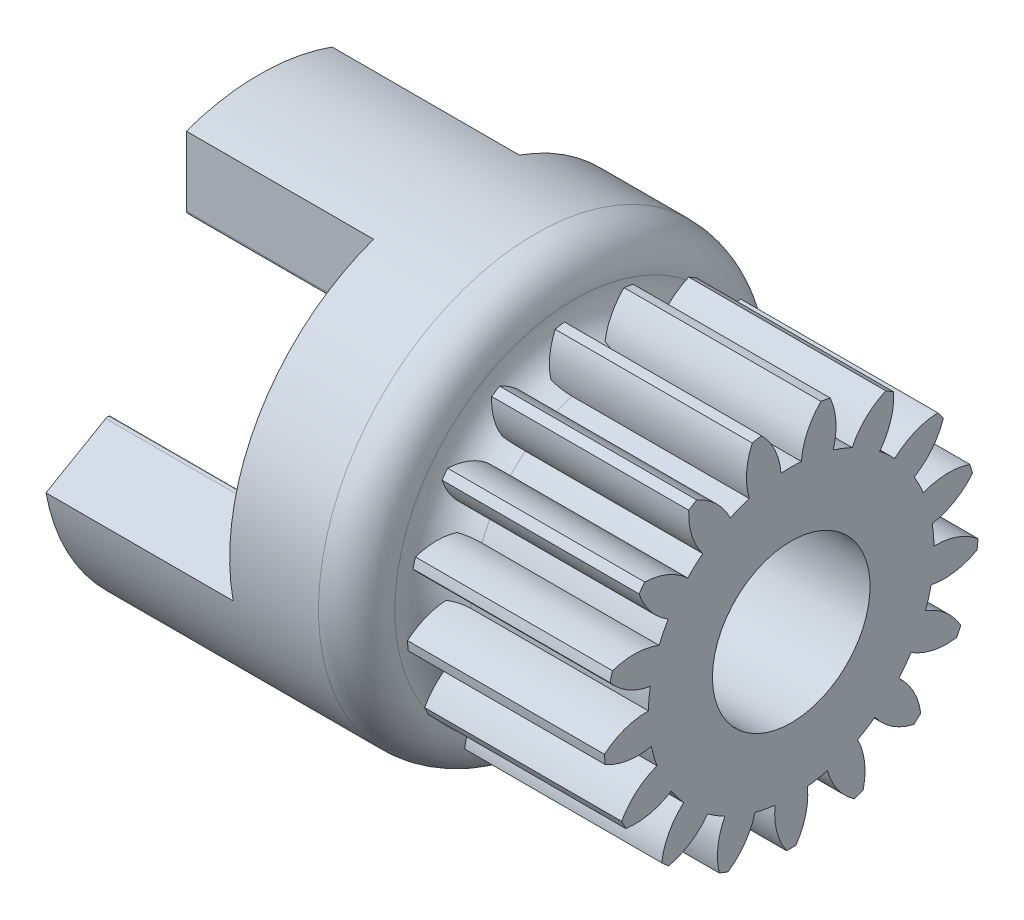
SolidWorks part; units mm, degrees
ref_plane "Plane1" through (0, 0, 0) normal (0, 0, 1) x (1, 0, 0)
ref_plane "Plane2" through (0, 0, 0) normal (0, 1, 0) x (1, 0, 0)
ref_plane "Plane3" through (0, 0, 0) normal (1, 0, 0) x (0, 0, -1)
sketch "HoldingSke" plane through (0, 0, 0) normal (0, 1, 0) x (1, 0, 0)
  line L0 (0, 0) -> (0.9563, -0.2924)
  line L1 (-15, 0) -> (100, 0) construction
  line L2 (0, 0) -> (-2.1039, 2.3779)
  line L3 (0, 0) -> (-11.863, 4.5341)
  line L4 (0, 0) -> (8.2586, 2.5249)
  line L5 (0, 0) -> (-46.8476, -17.4728)
  line L6 (0, 0) -> (-8.2896, -5.593)
  line L7 (-2.1039, 2.3779) -> (8.6586, 51.2059)
  line L8 (-76.2, 54.61) -> (-74.8, 54.61)
  line L9 (-71.009, 38.7566) -> (-53.1078, 45.2721)
  line L10 (-76.2, 71.12) -> (104.1128, 71.12)
  line L11 (0, 0) -> (-10, 0)
  line L12 (-76.2, 101.6) -> (-76.162, 101.6)
  line L13 (24.9733, 27.94) -> (52.9518, 28.4284)
  line L14 (24.9733, 27.94) -> (24.9743, 27.94)
  line L15 (24.9733, 27.94) -> (100.4006, 29.5858)
  line L16 (-63.627, -1) -> (-12.827, -1)
  circle A0 centre (0, 0) radius 4
  circle A1 centre (0, 0) radius 7.249
  circle A2 centre (0, 0) radius 37.5
  circle A3 centre (0, 0) radius 4
  dimension "Num_teeth" = 17
  dimension "Pitch_radius" = 180.3128
  dimension "Width" = 10
  dimension "Thickness" = 10
sketch "BasProSke" plane through (0, 0, 0) normal (0, 1, 0) x (1, 0, 0)
  line L0 (-10, 0) -> (60, 0) construction
  line L1 (0, 0) -> (0, 9.5)
  line L2 (0, 0) -> (10, 0)
  line L3 (10, 0) -> (10, 9.5)
  line L4 (10, 9.5) -> (0, 9.5)
  dimension "Thickness" = 10
  dimension "Diameter" = 19
revolve "Base-Revolve" add sketch "BasProSke" angle 360 about L0
sketch "TooCutSke" plane through (0, 0, 0) normal (1, 0, 0) x (0, 0, -1)
  line L1 (0, 0) -> (0, 107) construction
  line L2 (0, 0) -> (-0.8507, 8.4573) construction
  line L3 (0, 0) -> (-3.1126, 16.6509) construction
  line L4 (-0.8507, 8.4573) -> (-1.5563, 8.3254) construction
  arc A0 (0.5169, 7.2306) -> (-0.5169, 7.2306) centre (0, 0) ccw
  arc A1 (1.5331, 9.4012) -> (-1.5331, 9.4012) centre (0, 0) ccw
  circle A2 centre (0, 0) radius 8.5 construction
  circle A3 centre (0, 0) radius 7.9874 construction
  arc A4 (-0.5169, 7.2306) -> (-1.5331, 9.4012) centre (-3.9066, 6.9668) ccw
  arc A5 (1.5331, 9.4012) -> (0.5169, 7.2306) centre (3.9066, 6.9668) ccw
extrude "ToothCut" cut sketch "TooCutSke" along normal through all
fillet "Breaks" [suppressed] radius 0.02 tangent propagation no
fillet "RootFillets" [suppressed] radius 0.251
pattern_circular "TeethCuts" count 17 every 21.176 about axis through (-10, 0, 0) along (1, 0, 0) of "ToothCut", "RootFillets", "Breaks"
sketch "HubNeaOneSke" plane through (0, 0, 0) normal (-1, 0, 0) x (0, 0, 1)
  circle A0 centre (0, 0) radius 7.249
  dimension "Diameter" = 14.498
extrude "HubNearOne" [suppressed] add sketch "HubNeaOneSke" along normal blind 40.0001
sketch "HubNeaBotSke" plane through (0, 0, 0) normal (-1, 0, 0) x (0, 0, 1)
  circle A0 centre (0, 0) radius 7.249
  dimension "Diameter" = 14.498
extrude "HubNearBoth" [suppressed] add sketch "HubNeaBotSke" along normal blind 20
ref_plane "FarPln" through (10, 0, 0) normal (1, 0, 0) x (0, 0, -1)
sketch "HubFarSke" plane through (10, 0, 0) normal (1, 0, 0) x (0, 0, -1)
  circle A0 centre (0, 0) radius 7.249
  dimension "Diameter" = 14.498
extrude "HubFar" [suppressed] add sketch "HubFarSke" along normal blind 20
sketch "BorSke" plane through (0, 0, 0) normal (1, 0, 0) x (0, 0, -1)
  circle A0 centre (0, 0) radius 4
  dimension "Diameter" = 8
extrude "Bore" cut sketch "BorSke" along normal mid plane 100.0001
sketch "KeySke" plane through (0, 0, 0) normal (1, 0, 0) x (0, 0, -1)
  line L0 (-1.5, 0) -> (-1.5, 5.4)
  line L1 (-1.5, 5.4) -> (1.5, 5.4)
  line L2 (1.5, 5.4) -> (1.5, 0)
  line L3 (0, 0) -> (0, 34) construction
  line L4 (-1.5, 0) -> (1.5, 0)
  dimension "Width" = 3
extrude "Keyway" [suppressed] cut sketch "KeySke" along normal mid plane 100.0001
pattern_circular "Keyway2" [suppressed] count 2 every 90 about axis through (-10, 0, 0) along (1, 0, 0) reverse direction yes
sketch "Эскиз3" plane through (0, 0, 0) normal (-1, 0, 0) x (0, 0, 1)
  circle A0 centre (0, 0) radius 7.249
  circle A1 centre (0, 0) radius 4
  dimension "D1" = 8
  dimension "D2" = 14.498
extrude "Бобышка-Вытянуть1" add sketch "Эскиз3" along normal blind 1
sketch "Эскиз4" plane through (-1, 0, 0) normal (-1, 0, 0) x (0, 0, 1)
  circle A0 centre (0, 0) radius 11
  dimension "D1" = 22
extrude "Бобышка-Вытянуть2" add sketch "Эскиз4" along normal blind 16
sketch "Эскиз5" plane through (-17, 0, 0) normal (-1, 0, 0) x (0, 0, 1)
  line L0 (-3.7, 11.2717) -> (-3.7, 5.3442)
  line L3 (0, 0) -> (0, 14.8952) construction
  line L9 (-11.6115, -2.4315) -> (-6.4782, 0.5322)
  line L11 (11.6115, -2.4315) -> (6.4782, 0.5322)
  line L12 (3.7, 11.2717) -> (3.7, 5.3442)
  line L14 (-7.9115, -8.8401) -> (-2.7782, -5.8764)
  line L15 (7.9115, -8.8401) -> (2.7782, -5.8764)
  arc A3 (-3.7, 5.3442) -> (-6.4782, 0.5322) centre (0, 0) ccw
  arc A4 (-3.7, 11.2717) -> (-11.6115, -2.4315) centre (-3.7, 2.1362) ccw
  arc A6 (6.4782, 0.5322) -> (3.7, 5.3442) centre (0, 0) ccw
  arc A7 (11.6115, -2.4315) -> (3.7, 11.2717) centre (3.7, 2.1362) ccw
  arc A8 (-2.7782, -5.8764) -> (2.7782, -5.8764) centre (0, 0) ccw
  arc A9 (-7.9115, -8.8401) -> (7.9115, -8.8401) centre (0, -4.2724) ccw
  dimension "D1" = 3
extrude "Вырез-Вытянуть2" cut sketch "Эскиз5" against normal blind 9.5
sketch "Эскиз6" plane through (-17, 0, 0) normal (-1, 0, 0) x (0, 0, 1)
  circle A0 centre (0, 0) radius 7.5
extrude "Вырез-Вытянуть3" cut sketch "Эскиз6" against normal blind 10
fillet "Скругление1" radius 0.2 6 edges at (-12.25, -0.0576, -7.4998) (-12.25, -6.4662, 3.7998) (-12.25, -6.4662, -3.7998) (-12.25, -0.0576, 7.4998) (-12.25, 6.5238, 3.7) (-12.25, 6.5238, -3.7)
fillet "Скругление2" radius 2 1 edges at (-1, 0, 7.249)
fillet "Скругление3" radius 2 1 edges at (-1, 0, 11)
equation "' \"Module@HoldingSke\" = 6.35"
equation "' \"Num_teeth@HoldingSke\" = 12"
equation "' \"Ap@HoldingSke\" =  20"
equation "' \"Ap@HoldingSke\" = 20"
equation "' \"Width@HoldingSke\" = 0.5 * 25.4"
equation "' \"Hub_dia@HoldingSke\"= 1 * 25.4"
equation "' \"Hub_dia@HoldingSke\" = 1 * 25.4"
equation "' \"Overall_len@HoldingSke\" = 1.0 * 25.4"
equation "' \"Bore@HoldingSke\" = 0.75 * 25.4"
equation "' \"T_dim@HoldingSke\" = 0.1 * 25.4"
equation "' \"Width@KeySke\" = 0.25 * 25.4"
equation "' \"Show_teeth@HoldingSke\" = 13"
equation "' \"Backlash@HoldingSke\" = 0.009 * 25.4"
equation "' \"Addendum_fac@HoldingSke\" = 1.0"
equation "' \"Dedendum_fac@HoldingSke\" = 1.25"
equation "' \"Dedendum_add@HoldingSke\" = 0.00005 * 25.4"
equation "' \"Clearance_fac@HoldingSke\" = 0.25"
equation "\"Pitch@HoldingSke\" = 1 / \"Module@HoldingSke\""
equation "\"Overcut_dia@TooCutSke\" = (\"Num_teeth@HoldingSke\" + 2 * \"Addendum_fac@HoldingSke\") / \"Pitch@HoldingSke\" + 0.002 * 25.4"
equation "\"Pitch_dia@TooCutSke\" = \"Num_teeth@HoldingSke\" / \"Pitch@HoldingSke\""
equation "\"Base_dia@TooCutSke\" = \"Num_teeth@HoldingSke\" / \"Pitch@HoldingSke\" * cos((\"Ap@HoldingSke\"  * 3.14159265 / 180))"
equation "\"Root_dia@TooCutSke\" = (\"Num_teeth@HoldingSke\" + 2) / \"Pitch@HoldingSke\" - 2 * (\"Addendum_fac@HoldingSke\" + \"Dedendum_fac@HoldingSke\") / \"Pitch@HoldingSke\" - \"Dedendum_add@HoldingSke\" * 2"
equation "\"Half_ang@TooCutSke\" = 180 / \"Num_teeth@HoldingSke\""
equation "\"Half_CT@TooCutSke\" = \"Num_teeth@HoldingSke\" / \"Pitch@HoldingSke\" * sin((3.14159265 / 2 / \"Num_teeth@HoldingSke\")) / 2 - 7 * \"Backlash@HoldingSke\" / 4"
equation "\"Flank_rad@TooCutSke\" = \"Num_teeth@HoldingSke\" / \"Pitch@HoldingSke\" / 5"
equation "\"Radius@RootFillets\" = \"Clearance_fac@HoldingSke\" / \"Pitch@HoldingSke\" + \"Dedendum_add@HoldingSke\""
equation "\"Break_rad@Breaks\" = 0.02 / \"Pitch@HoldingSke\""
equation "\"Thickness@HoldingSke\" = \"Width@HoldingSke\""
equation "\"OAL@HoldingSke\" = \"Thickness@HoldingSke\""
equation "\"MHD@HoldingSke\" = (\"Num_teeth@HoldingSke\" + 2) / \"Pitch@HoldingSke\" - 2 * (\"Addendum_fac@HoldingSke\" + \"Dedendum_fac@HoldingSke\")  / \"Pitch@HoldingSke\" - \"Dedendum_add@HoldingSke\" * 2"
equation "\"MBD@HoldingSke\" = (\"Num_teeth@HoldingSke\" + 2) / \"Pitch@HoldingSke\" - 2 * (\"Addendum_fac@HoldingSke\" + \"Dedendum_fac@HoldingSke\")  / \"Pitch@HoldingSke\" - \"Dedendum_add@HoldingSke\" * 2 - 0.002 * 25.4"
equation "\"MHD@HoldingSke\" = ((sgn( \"MHD@HoldingSke\" - \"Hub_dia@HoldingSke\" )-1)*( \"MHD@HoldingSke\" - \"Hub_dia@HoldingSke\" ))/-2+ \"Hub_dia@HoldingSke\""
equation "\"MBD@HoldingSke\" = ((sgn( \"MBD@HoldingSke\" - \"Bore@HoldingSke\" )-1)*( \"MBD@HoldingSke\" - \"Bore@HoldingSke\" ))/-2+ \"Bore@HoldingSke\""
equation "\"OAL@HoldingSke\" = ((sgn( \"OAL@HoldingSke\" - \"Overall_len@HoldingSke\" )+1)*( \"OAL@HoldingSke\" - \"Overall_len@HoldingSke\" ))/2 + \"Overall_len@HoldingSke\" + 0.000002 * 25.4"
equation "\"Num_teeth@TeethCuts\" = int( \"Show_teeth@HoldingSke\" ) + 1"
equation "\"Num_teeth@TeethCuts\" = ((sgn( \"Num_teeth@TeethCuts\" - \"Num_teeth@HoldingSke\" )-1)*( \"Num_teeth@TeethCuts\" - \"Num_teeth@HoldingSke\" ))/-2+ \"Num_teeth@HoldingSke\""
equation "\"Num_teeth@TeethCuts\" = ((sgn( \"Num_teeth@TeethCuts\" - 2.0)+1)*( \"Num_teeth@TeethCuts\" - 2.0))/2 +2.0"
equation "\"Angle@TeethCuts\" = 360.0 / \"Num_teeth@HoldingSke\""
equation "\"Diameter@BasProSke\" = (\"Num_teeth@HoldingSke\" + 2 * \"Addendum_fac@HoldingSke\") / \"Pitch@HoldingSke\""
equation "\"Thickness@BasProSke\"  = \"Thickness@HoldingSke\""
equation "' \"Fillet_rad@BasProSke\" =  \"Thickness@HoldingSke\" * 0.05"
equation "' \"Fillet_rad@BasProSke\" = \"Thickness@HoldingSke\" * 0.05"
equation "\"MHD@HoldingSke\" = ((sgn( \"MHD@HoldingSke\" - \"Root_dia@TooCutSke\" )-1)*( \"MHD@HoldingSke\" - \"Root_dia@TooCutSke\" ))/-2+ \"Root_dia@TooCutSke\""
equation "\"Diameter@HubNeaOneSke\" = \"MHD@HoldingSke\""
equation "\"Length@HubNearOne\" = \"OAL@HoldingSke\" - \"Thickness@BasProSke\""
equation "\"Diameter@HubNeaBotSke\" = \"MHD@HoldingSke\""
equation "\"Length@HubNearBoth\" = ( \"OAL@HoldingSke\" - \"Thickness@BasProSke\" ) / 2.0"
equation "\"Thickness@FarPln\" = \"Thickness@BasProSke\""
equation "\"Diameter@HubFarSke\" = \"MHD@HoldingSke\""
equation "\"Length@HubFar\" = ( \"OAL@HoldingSke\" - \"Thickness@BasProSke\" ) / 2.0"
equation "\"Diameter@BorSke\" = \"MBD@HoldingSke\""
equation "\"D1@Bore\" = \"OAL@HoldingSke\" * 2.0"
equation "\"D1@Keyway\" = \"OAL@HoldingSke\" * 2.0"
equation "\"Offset@KeySke\" = \"T_dim@HoldingSke\" + \"MBD@HoldingSke\" / 2.0"
